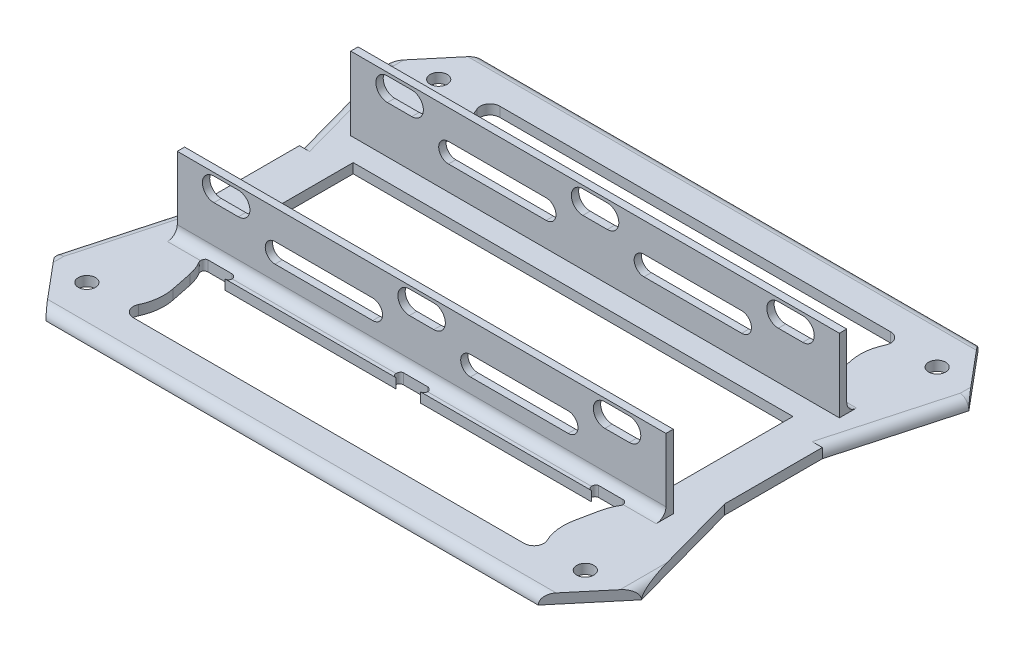
SolidWorks part; units mm, degrees
material "ABS"
ref_plane "Front Plane" through (0, 0, 0) normal (0, 0, 1) x (1, 0, 0)
ref_plane "Top Plane" through (0, 0, 0) normal (0, 1, 0) x (1, 0, 0)
ref_plane "Right Plane" through (0, 0, 0) normal (1, 0, 0) x (0, 0, -1)
sketch "Sketch1" plane through (0, 0, 0) normal (0, 1, 0) x (1, 0, 0)
  line L0 (0, 0) -> (0, 45) construction
  line L1 (-60, -45) -> (60, -45)
  line L2 (-60, -45) -> (-60, 45)
  line L3 (-60, 45) -> (60, 45)
  line L4 (60, -45) -> (60, 45)
  line L5 (-60, -45) -> (60, 45) construction
  line L6 (-60, 45) -> (60, -45) construction
  line L8 (-60, -13) -> (-60, 13)
  point P0 (0, 0)
  point P6 (-44.5, 0)
  point P12 (-60, 0)
  point P22 (0, 0)
  dimension "D2" = 26
  dimension "D3" = 15.5
  dimension "D13" = 120
  dimension "D14" = 90
extrude "Boss-Extrude1" add sketch "Sketch1" along normal blind 2 contours L4 L3 L2 L1 | L2 | L4 region at (0, 0, 0)
sketch "Sketch17" plane through (0, 2, 0) normal (0, 1, 0) x (1, 0, 0)
  line L0 (-60, -45) -> (-60, 45) construction
  line L7 (-60, 45) -> (60, 45) construction
  circle A3 centre (-56, 41) radius 1.75
  dimension "D1" = 3.5
  dimension "D2" = 4
  dimension "D3" = 4
extrude "Cut-Extrude11" cut sketch "Sketch17" against normal blind 4
mirror "Mirror13" about plane through (0, 0, 0) normal (1, 0, 0) of "Cut-Extrude11"
mirror "Mirror14" about plane through (0, 0, 0) normal (0, 0, 1) of "Mirror13"
sketch "Sketch19" plane through (0, 2, 0) normal (0, 1, 0) x (1, 0, 0)
  line L0 (-51.5, 10) -> (-50, 10)
  line L5 (-50, -17) -> (50, 17) construction
  line L6 (-50, 17) -> (50, -17) construction
  line L7 (-50, 17) -> (50, 17)
  line L8 (-50, 17) -> (-50, 18.5)
  line L9 (-50, 18.5) -> (50, 18.5)
  line L10 (50, 17) -> (50, 18.5)
  line L12 (50, 10) -> (50, -10)
  line L14 (51.5, 10) -> (51.5, -10)
  line L15 (-50, -17) -> (50, -17)
  line L16 (-50, -17) -> (-50, -18.5)
  line L17 (-50, -18.5) -> (50, -18.5)
  line L18 (50, -17) -> (50, -18.5)
  line L20 (-50, 10) -> (-50, -10)
  line L22 (-51.5, 10) -> (-51.5, -10)
  line L23 (50, 10) -> (51.5, 10)
  line L24 (-55, 0) -> (55, 0) construction
  line L25 (50, -10) -> (51.5, -10)
  line L26 (-51.5, -10) -> (-50, -10)
  point P0 (0, 0)
  dimension "D1" = 100
  dimension "D2" = 34
  dimension "D3" = 1.5
  dimension "D5" = 1.5
  dimension "D7" = 10
extrude "Boss-Extrude4" add sketch "Sketch19" along normal blind 15
sketch "Sketch20" plane through (0, 0, 18.5) normal (0, 0, 1) x (1, 0, 0)
  line L0 (-42.5, 14) -> (-37.5, 14) construction
  line L1 (-42.5, 16.3573) -> (-37.5, 16.3573)
  line L2 (-42.5, 11.6427) -> (-37.5, 11.6427)
  line L3 (-50, 17) -> (50, 17) construction
  line L4 (-50, 17) -> (-50, 2) construction
  line L5 (-2.5, 11.6427) -> (2.5, 11.6427)
  line L6 (-2.5, 16.3573) -> (2.5, 16.3573)
  line L7 (-2.5, 14) -> (2.5, 14) construction
  line L8 (37.5, 11.6427) -> (42.5, 11.6427)
  line L9 (37.5, 16.3573) -> (42.5, 16.3573)
  line L10 (37.5, 14) -> (42.5, 14) construction
  arc A0 (-42.5, 16.3573) -> (-42.5, 11.6427) centre (-42.5, 14) ccw
  arc A1 (-37.5, 11.6427) -> (-37.5, 16.3573) centre (-37.5, 14) ccw
  arc A2 (-2.5, 16.3573) -> (-2.5, 11.6427) centre (-2.5, 14) ccw
  arc A3 (2.5, 11.6427) -> (2.5, 16.3573) centre (2.5, 14) ccw
  arc A4 (37.5, 16.3573) -> (37.5, 11.6427) centre (37.5, 14) ccw
  arc A5 (42.5, 11.6427) -> (42.5, 16.3573) centre (42.5, 14) ccw
  point P2 (-40, 14)
  point P14 (0, 14)
  point P21 (40, 14)
  dimension "D1" = 3
  dimension "D2" = 10
  dimension "D3" = 5
  dimension "D4" = 3
extrude "Cut-Extrude12" cut sketch "Sketch20" against normal blind 38
sketch "Sketch21" plane through (0, 2, 0) normal (0, 1, 0) x (1, 0, 0)
  line L0 (-42.5, -20.5) -> (-37.5, -20.5) construction
  line L1 (-42.5, -19.7542) -> (-37.5, -19.7542)
  line L2 (-42.5, -21.2458) -> (-37.5, -21.2458)
  line L3 (-50, -18.5) -> (50, -18.5) construction
  line L4 (-2.5, -21.2458) -> (2.5, -21.2458)
  line L5 (-2.5, -19.7542) -> (2.5, -19.7542)
  line L6 (-2.5, -20.5) -> (2.5, -20.5) construction
  line L7 (37.5, -21.2458) -> (42.5, -21.2458)
  line L8 (37.5, -19.7542) -> (42.5, -19.7542)
  line L9 (37.5, -20.5) -> (42.5, -20.5) construction
  line L10 (-55, 0) -> (55, 0) construction
  line L11 (37.5, 20.5) -> (42.5, 20.5) construction
  line L12 (37.5, 19.7542) -> (42.5, 19.7542)
  line L13 (37.5, 21.2458) -> (42.5, 21.2458)
  line L14 (-2.5, 20.5) -> (2.5, 20.5) construction
  line L15 (-2.5, 19.7542) -> (2.5, 19.7542)
  line L16 (-2.5, 21.2458) -> (2.5, 21.2458)
  line L17 (-42.5, 20.5) -> (-37.5, 20.5) construction
  line L18 (-42.5, 19.7542) -> (-37.5, 19.7542)
  line L19 (-42.5, 21.2458) -> (-37.5, 21.2458)
  arc A0 (-42.5, -19.7542) -> (-42.5, -21.2458) centre (-42.5, -20.5) ccw
  arc A1 (-37.5, -21.2458) -> (-37.5, -19.7542) centre (-37.5, -20.5) ccw
  arc A2 (-2.5, -19.7542) -> (-2.5, -21.2458) centre (-2.5, -20.5) ccw
  arc A3 (2.5, -21.2458) -> (2.5, -19.7542) centre (2.5, -20.5) ccw
  arc A4 (37.5, -19.7542) -> (37.5, -21.2458) centre (37.5, -20.5) ccw
  arc A5 (42.5, -21.2458) -> (42.5, -19.7542) centre (42.5, -20.5) ccw
  arc A6 (37.5, 19.7542) -> (37.5, 21.2458) centre (37.5, 20.5) cw
  arc A7 (42.5, 21.2458) -> (42.5, 19.7542) centre (42.5, 20.5) cw
  arc A8 (-2.5, 19.7542) -> (-2.5, 21.2458) centre (-2.5, 20.5) cw
  arc A9 (2.5, 21.2458) -> (2.5, 19.7542) centre (2.5, 20.5) cw
  arc A10 (-42.5, 19.7542) -> (-42.5, 21.2458) centre (-42.5, 20.5) cw
  arc A11 (-37.5, 21.2458) -> (-37.5, 19.7542) centre (-37.5, 20.5) cw
  point P2 (-40, -20.5)
  point P14 (0, -20.5)
  point P21 (40, -20.5)
  point P28 (40, 20.5)
  point P35 (0, 20.5)
  point P42 (-40, 20.5)
  dimension "D1" = 10
  dimension "D2" = 5
  dimension "D3" = 2
  dimension "D4" = 3
extrude "Cut-Extrude13" cut sketch "Sketch21" against normal blind 38
fillet "Fillet1" radius 2 4 edges at (51.5, 2, 0) (0, 2, -18.5) (0, 2, 18.5) (-51.5, 2, 0)
sketch "Sketch23" plane through (0, 2, 0) normal (0, 1, 0) x (1, 0, 0)
  line L0 (40, -35.5) -> (-40, -35.5) construction
  line L1 (45, 12.5) -> (-45, 12.5)
  line L2 (45, 12.5) -> (45, -12.5)
  line L3 (45, -12.5) -> (-45, -12.5)
  line L4 (-45, 12.5) -> (-45, -12.5)
  line L5 (45, 12.5) -> (-45, -12.5) construction
  line L6 (45, -12.5) -> (-45, 12.5) construction
  line L7 (40, -37.5) -> (-40, -37.5)
  line L8 (40, -33.5) -> (-40, -33.5)
  line L9 (36.7542, -20.5) -> (3.2458, -20.5) construction
  line L10 (-55, 0) -> (55, 0) construction
  line L11 (40, 35.5) -> (-40, 35.5) construction
  line L12 (40, 37.5) -> (-40, 37.5)
  line L13 (40, 33.5) -> (-40, 33.5)
  line L14 (60, -33.5) -> (53.5, -10)
  line L15 (60, -45) -> (60, 45) construction
  line L16 (53.5, -10) -> (53.5, 10)
  line L17 (53.5, 10) -> (60, 33.5)
  line L18 (60, 33.5) -> (60, -33.5)
  line L19 (0, -55) -> (0, 55) construction
  line L20 (-53.5, 10) -> (-60, 33.5)
  line L21 (-53.5, -10) -> (-53.5, 10)
  line L22 (-60, -33.5) -> (-53.5, -10)
  line L23 (-60, 33.5) -> (-60, -33.5)
  arc A0 (40, -37.5) -> (40, -33.5) centre (40, -35.5) ccw
  arc A1 (-40, -33.5) -> (-40, -37.5) centre (-40, -35.5) ccw
  arc A2 (40, 37.5) -> (40, 33.5) centre (40, 35.5) cw
  arc A3 (-40, 33.5) -> (-40, 37.5) centre (-40, 35.5) cw
  point P0 (0, 0)
  point P8 (0, -35.5)
  point P21 (0, 35.5)
  dimension "D4" = 2
  dimension "D1" = 25
  dimension "D2" = 90
  dimension "D3" = 15
  dimension "D5" = 80
extrude "Cut-Extrude15" cut sketch "Sketch23" against normal blind 4
fillet "Fillet2" radius 3 4 edges at (60, 1, 45) (-60, 1, 45) (-60, 1, -45) (60, 1, -45)
fillet "Fillet3" radius 2 13 edges at (-60, 2, -37.75) (-59.1213, 2, -44.1213) (60, 2, -37.75) (59.1213, 2, -44.1213) (-60, 2, 37.75) (-59.1213, 2, 44.1213) (60, 2, 37.75) (59.1213, 2, 44.1213) (-56.75, 2, -21.75) (0, 2, -45) (56.75, 2, -21.75) (0, 2, 45) (-56.75, 2, 21.75)
sketch "Sketch24" plane through (0, 0, 18.5) normal (0, 0, 1) x (1, 0, 0)
  line L0 (-30, 9) -> (-10, 9) construction
  line L1 (-30, 11) -> (-10, 11)
  line L2 (-30, 7) -> (-10, 7)
  line L3 (-50, 4) -> (50, 4) construction
  line L4 (0, -55) -> (0, 55) construction
  line L5 (30, 9) -> (10, 9) construction
  line L6 (30, 11) -> (10, 11)
  line L7 (30, 7) -> (10, 7)
  arc A0 (-30, 11) -> (-30, 7) centre (-30, 9) ccw
  arc A1 (-10, 7) -> (-10, 11) centre (-10, 9) ccw
  arc A2 (30, 11) -> (30, 7) centre (30, 9) cw
  arc A3 (10, 7) -> (10, 11) centre (10, 9) cw
  point P2 (-20, 9)
  point P14 (20, 9)
  dimension "D3" = 2
  dimension "D1" = 20
  dimension "D2" = 5
  dimension "D4" = 20
extrude "Cut-Extrude16" cut sketch "Sketch24" against normal blind 38 contours L6 A3 L7 A2 | L2 A1 L1 A0
sketch "Sketch25" plane through (0, 2, 0) normal (0, 1, 0) x (1, 0, 0)
  circle A0 centre (51, -36) radius 1.75
  dimension "D3" = 3.5
extrude "Cut-Extrude17" cut sketch "Sketch25" against normal blind 3
mirror "Mirror15" about plane through (0, 0, 0) normal (1, 0, 0) of "Cut-Extrude17"
mirror "Mirror16" about plane through (0, 0, 0) normal (0, 0, 1) of "Mirror15"
sketch "Sketch26" plane through (51.5, 0, 0) normal (1, 0, 0) x (0, 0, -1)
  line L0 (10, 17) -> (10, 4) construction
  line L5 (-10, 17) -> (10, 17)
  line L6 (-10, 17) -> (-10, 2)
  line L7 (-10, 2) -> (10, 2)
  line L8 (10, 17) -> (10, 2)
  dimension "D1" = 15
extrude "Cut-Extrude18" cut sketch "Sketch26" against normal mid plane 233
sketch "Sketch27" plane through (0, 0, 0) normal (0, -1, 0) x (1, 0, 0)
  line L0 (40, -33.5) -> (42.5, -21.2458)
  line L1 (42.5, -21.2458) -> (-42.5, -21.2458)
  line L2 (-42.5, -21.2458) -> (-40, -33.5)
  line L3 (-40, -33.5) -> (40, -33.5)
extrude "Cut-Extrude19" cut sketch "Sketch27" against normal blind 10
mirror "Mirror17" about plane through (0, 0, 0) normal (0, 0, 1) of "Cut-Extrude19"
sketch "Sketch28" plane through (0, 0, 0) normal (0, -1, 0) x (1, 0, 0)
  line L0 (-60, 33.5) -> (-50.3633, 45)
  line L1 (-57, 45) -> (57, 45) construction
  line L6 (-60, -33.5) -> (-50.3633, -45)
  line L7 (-57, -45) -> (57, -45) construction
  line L8 (0, -9.35) -> (0, 9.35) construction
  line L9 (60, -33.5) -> (50.3633, -45)
  line L13 (60, 33.5) -> (50.3633, 45)
  line L15 (-50.3633, -45) -> (50.3633, -45)
  line L16 (-50.3633, 45) -> (-60, 45)
  line L17 (-60, 45) -> (-60, 33.5)
  line L18 (60, 45) -> (60, 33.5)
  line L19 (50.3633, 45) -> (60, 45)
  line L20 (9.35, 0) -> (-9.35, 0) construction
  line L21 (50.3633, -45) -> (60, -45)
  line L22 (60, -33.5) -> (50.3633, -45)
  line L23 (60, -45) -> (60, -33.5)
  line L24 (-60, -45) -> (-60, -33.5)
  line L25 (-50.3633, -45) -> (-60, -45)
  line L26 (-60, -33.5) -> (-50.3633, -45)
extrude "Cut-Extrude20" cut sketch "Sketch28" against normal blind 10 contours L16 L17 L0 | L19 L13 L18 | L25 L6 L24 | L21 L23 L9 region at (-56.7878, 0, 41.1667) region at (56.7878, 0, -41.1667) region at (-56.7878, 0, -41.1667) region at (56.7878, 0, 41.1667)
fillet "Fillet4" radius 10 4 edges at (40, 1, -33.5) (-40, 1, -33.5) (-40, 1, 33.5) (40, 1, 33.5)
fillet "Fillet5" radius 10 4 edges at (-42.5, 1, 21.2458) (42.5, 1, 21.2458) (42.5, 1, -21.2458) (-42.5, 1, -21.2458)
